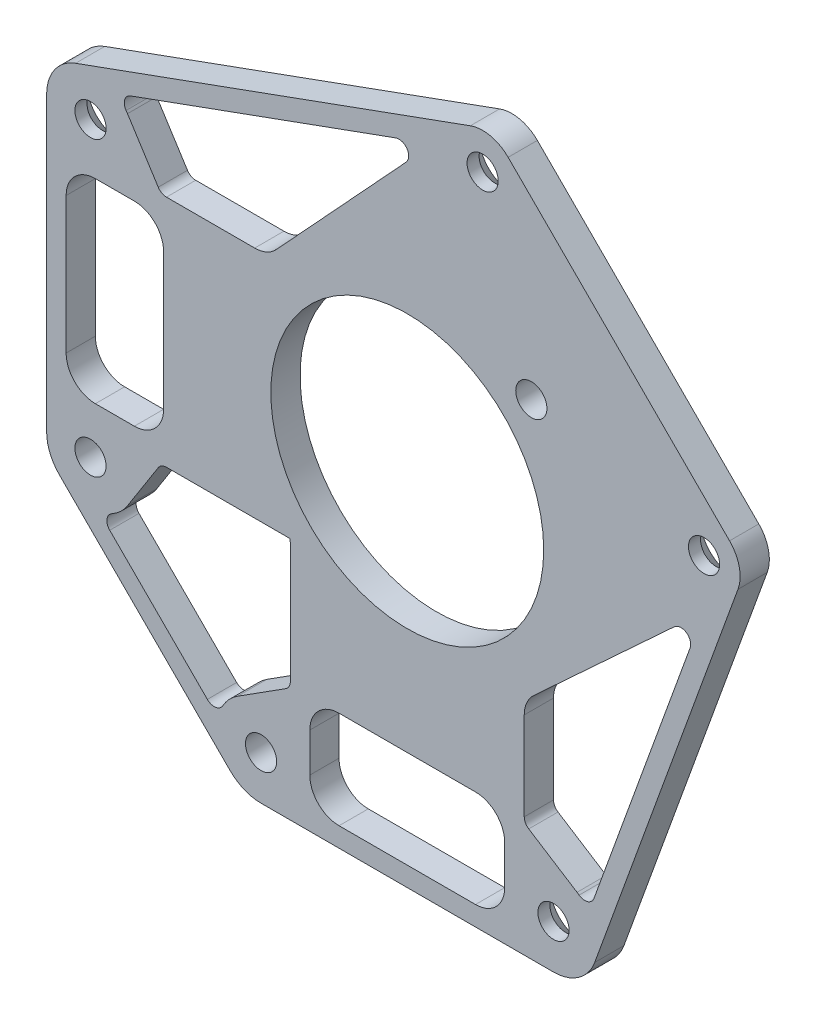
SolidWorks part; units mm, degrees
material "6061-T6 (SS)"
ref_plane "Front Plane" through (0, 0, 0) normal (0, 0, 1) x (1, 0, 0)
ref_plane "Top Plane" through (0, 0, 0) normal (0, 1, 0) x (1, 0, 0)
ref_plane "Right Plane" through (0, 0, 0) normal (1, 0, 0) x (0, 0, -1)
sketch "Sketch1" plane through (0, 0, 0) normal (0, 0, 1) x (1, 0, 0)
  line L0 (-7.7139, 20.2317) -> (-27.0698, -0.7279)
  line L1 (-2.3793, 20.3378) -> (20.3378, -2.3793)
  line L2 (0, 0) -> (-12.7279, -12.7279) construction
  line L8 (-49.7279, -19.7279) -> (-49.7279, -5.7279)
  line L9 (-44.7279, -22.7279) -> (-40.7279, -22.7279)
  line L10 (-47.7279, -19.7279) -> (-47.7279, -5.7279)
  line L11 (-44.7279, -2.7279) -> (-40.7279, -2.7279)
  line L12 (-37.7279, -19.7279) -> (-37.7279, -5.7279)
  line L13 (-47.7279, -22.7279) -> (-37.7279, -2.7279) construction
  line L14 (-47.7279, -2.7279) -> (-37.7279, -22.7279) construction
  line L19 (-44.7279, -0.7279) -> (-40.7279, -0.7279)
  line L21 (-44.7279, -24.7279) -> (-40.7279, -24.7279)
  line L22 (-40.7279, -0.7279) -> (-27.0698, -0.7279)
  line L23 (-40.7279, -24.7279) -> (-24.7695, -24.7279)
  line L24 (20.2317, -7.7139) -> (-0.7279, -27.0698)
  line L25 (-35.7279, -19.7279) -> (-35.7279, -5.7279) construction
  line L26 (-24.7279, -40.7279) -> (-24.7279, -24.7695)
  line L27 (-0.7279, -40.7279) -> (-0.7279, -27.0698)
  line L28 (-2.7279, -47.7279) -> (-22.7279, -37.7279) construction
  line L29 (-22.7279, -47.7279) -> (-2.7279, -37.7279) construction
  line L30 (-24.7279, -44.7279) -> (-24.7279, -40.7279)
  line L31 (-0.7279, -44.7279) -> (-0.7279, -40.7279)
  line L32 (-19.7279, -37.7279) -> (-5.7279, -37.7279)
  line L33 (-2.7279, -44.7279) -> (-2.7279, -40.7279)
  line L34 (-19.7279, -47.7279) -> (-5.7279, -47.7279)
  line L35 (-22.7279, -44.7279) -> (-22.7279, -40.7279)
  line L36 (-19.7279, -49.7279) -> (-5.7279, -49.7279)
  arc A0 (-3.7936, 16.5194) -> (-6.1977, 18.9236) centre (-4.9956, 17.7215) ccw construction
  arc A1 (-6.1977, 18.9236) -> (-3.7936, 16.5194) centre (-4.9956, 17.7215) ccw construction
  arc A2 (-3.7936, 16.5194) -> (-6.1977, 18.9236) centre (-4.9956, 17.7215) ccw construction
  arc A3 (-6.1977, 18.9236) -> (-3.7936, 16.5194) centre (-4.9956, 17.7215) ccw construction
  circle A8 centre (-12.7279, -12.7279) radius 12.7 construction
  circle A9 centre (-12.7279, -12.7279) radius 12.7 construction
  circle A10 centre (-12.7279, -12.7279) radius 14
  arc A11 (-2.3793, 20.3378) -> (-7.7139, 20.2317) centre (-4.9956, 17.7215) ccw
  arc A13 (-24.7695, -24.7279) -> (-24.7279, -24.7695) centre (-12.7279, -12.7279) ccw
  arc A14 (-44.7279, -22.7279) -> (-47.7279, -19.7279) centre (-44.7279, -19.7279) cw
  arc A15 (-40.7279, -22.7279) -> (-37.7279, -19.7279) centre (-40.7279, -19.7279) ccw
  arc A16 (-40.7279, -2.7279) -> (-37.7279, -5.7279) centre (-40.7279, -5.7279) cw
  arc A17 (-47.7279, -5.7279) -> (-44.7279, -2.7279) centre (-44.7279, -5.7279) cw
  arc A18 (-49.7279, -5.7279) -> (-44.7279, -0.7279) centre (-44.7279, -5.7279) cw
  arc A21 (-44.7279, -24.7279) -> (-49.7279, -19.7279) centre (-44.7279, -19.7279) cw
  arc A22 (-40.7279, -24.7279) -> (-35.7279, -19.7279) centre (-40.7279, -19.7279) ccw construction
  arc A23 (-40.7279, -0.7279) -> (-35.7279, -5.7279) centre (-40.7279, -5.7279) cw construction
  arc A24 (-24.7279, -44.7279) -> (-19.7279, -49.7279) centre (-19.7279, -44.7279) ccw
  arc A25 (-5.7279, -49.7279) -> (-0.7279, -44.7279) centre (-5.7279, -44.7279) ccw
  arc A26 (-5.7279, -47.7279) -> (-2.7279, -44.7279) centre (-5.7279, -44.7279) ccw
  arc A27 (-2.7279, -40.7279) -> (-5.7279, -37.7279) centre (-5.7279, -40.7279) ccw
  arc A28 (-22.7279, -40.7279) -> (-19.7279, -37.7279) centre (-19.7279, -40.7279) cw
  arc A29 (-22.7279, -44.7279) -> (-19.7279, -47.7279) centre (-19.7279, -44.7279) ccw
  arc A30 (16.5194, -3.7936) -> (18.9236, -6.1977) centre (17.7215, -4.9956) cw construction
  arc A31 (18.9236, -6.1977) -> (16.5194, -3.7936) centre (17.7215, -4.9956) cw construction
  arc A32 (20.3378, -2.3793) -> (20.2317, -7.7139) centre (17.7215, -4.9956) cw
  point P0 (-42.7279, -12.7279)
  point P5 (0, 0)
  point P20 (0, 0)
  point P42 (0, 0)
  point P63 (-12.7279, -42.7279)
  point P83 (8.9792, 8.9792)
  dimension "D2" = 28
  dimension "D3" = 2
  dimension "D4" = 3
  dimension "D5" = 18.7
  dimension "D9" = 3
  dimension "D6" = 30
  dimension "D7" = 10
  dimension "D8" = 20
  dimension "D10" = 2
extrude "Boss-Extrude1" add sketch "Sketch1" along normal blind 3
fillet "Fillet1" radius 3 3 edges at (-0.7279, -27.0698, 1.5) (-24.7279, -24.7695, 1.5) (-27.0698, -0.7279, 1.5)
hole_wizard "M3 Clearance Hole1" positions "Sketch2" profile "Sketch3" hole size "M3" standard "ANSI Metric" end condition up to next
sketch "Sketch2" plane through (0, 0, 0) normal (0, 0, -1) x (-1, 0, 0)
  point P7 (0, 0)
sketch "Sketch3" plane through (0, 0, 0) normal (1, 0, 0) x (0, 1, 0)
  line L0 (0, 0) -> (0, 3)
  line L1 (0, 3) -> (1.6, 3)
  line L2 (1.6, 3) -> (1.6, 0)
  line L5 (1.6, 0) -> (0, 0)
  line L11 (0, -6.35) -> (0, 107.95) construction
  dimension "Thru Hole Dia." = 3.2
  dimension "Thru Hole Depth" = 3
hole_wizard "CSK for M3 SFHCS1" positions "Sketch4" profile "Sketch5" countersink size "M3" standard "ANSI Metric" end condition up to next
sketch "Sketch4" plane through (0, 0, 0) normal (0, 0, -1) x (-1, 0, 0)
  point P3 (4.9956, 17.7215)
  point P8 (-17.7215, -4.9956)
sketch "Sketch5" plane through (-4.9956, 17.7215, 0) normal (1, 0, 0) x (0, 1, 0)
  line L0 (0, 0) -> (0, 3)
  line L1 (0, 3) -> (1.6, 3)
  line L2 (1.6, 3) -> (1.6, 1.76)
  line L3 (1.6, 1.76) -> (3.36, 0)
  line L5 (3.36, 0) -> (0, 0)
  line L6 (-1.6, 1.76) -> (-3.36, 0) construction
  line L11 (0, -6.35) -> (0, 107.95) construction
  dimension "Thru Hole Dia." = 3.2
  dimension "Thru Hole Depth" = 3
  dimension "Near C'Sink Dia." = 6.72
  dimension "Near C'Sink Angle" = 90
sketch "Sketch8" plane through (0, 0, 3) normal (0, 0, 1) x (1, 0, 0)
  line L0 (-45.2279, -12.7279) -> (-45.2279, 2.2721) construction
  line L1 (-49.7279, -19.7279) -> (-49.7279, -5.7279) construction
  line L2 (-44.7279, -2.7279) -> (-40.7279, -2.7279) construction
  line L3 (-49.7279, 2.2721) -> (-49.7279, -5.7279)
  line L7 (-45.2279, -12.7279) -> (-42.7279, -12.7279) construction
  line L10 (-41.4318, 4.6886) -> (-37.9837, -0.7279)
  line L12 (-42.7279, -12.7279) -> (-42.7279, -2.7279) construction
  line L13 (-40.7279, -0.7279) -> (-27.0698, -0.7279) construction
  line L14 (-44.7279, -0.7279) -> (-37.9837, -0.7279)
  line L15 (-41.4318, -30.1445) -> (-37.9837, -24.7279)
  line L16 (-44.7279, -24.7279) -> (-37.9837, -24.7279)
  line L17 (-49.7279, -27.7279) -> (-49.7279, -19.7279)
  arc A0 (-41.4318, 4.6886) -> (-49.7279, 2.2721) centre (-45.2279, 2.2721) ccw
  arc A3 (-44.7279, -0.7279) -> (-49.7279, -5.7279) centre (-44.7279, -5.7279) ccw construction
  arc A4 (-44.7279, -0.7279) -> (-49.7279, -5.7279) centre (-44.7279, -5.7279) ccw
  arc A7 (-40.7279, -0.7279) -> (-35.7279, -5.7279) centre (-40.7279, -5.7279) cw construction
  arc A8 (-44.7279, -24.7279) -> (-49.7279, -19.7279) centre (-44.7279, -19.7279) cw
  arc A9 (-41.4318, -30.1445) -> (-49.7279, -27.7279) centre (-45.2279, -27.7279) cw
  dimension "D2" = 9
  dimension "D1" = 5
extrude "Boss-Extrude3" add sketch "Sketch8" against normal up to surface (3 mm away) up to face at (-8.3556, 17.7215, 0)
hole_wizard "CSK for M3 SFHCS2" positions "Sketch9" profile "Sketch10" countersink size "M3" standard "ANSI Metric" end condition up to next
sketch "Sketch9" plane through (0, 0, 0) normal (0, 0, -1) x (-1, 0, 0)
  point P0 (45.2279, 2.2721)
sketch "Sketch10" plane through (-45.2279, 2.2721, 0) normal (1, 0, 0) x (0, 1, 0)
  line L0 (0, 0) -> (0, 3)
  line L1 (0, 3) -> (1.6, 3)
  line L2 (1.6, 3) -> (1.6, 1.76)
  line L3 (1.6, 1.76) -> (3.36, 0)
  line L5 (3.36, 0) -> (0, 0)
  line L6 (-1.6, 1.76) -> (-3.36, 0) construction
  line L11 (0, -6.35) -> (0, 107.95) construction
  dimension "Thru Hole Dia." = 3.2
  dimension "Thru Hole Depth" = 3
  dimension "Near C'Sink Dia." = 6.72
  dimension "Near C'Sink Angle" = 90
hole_wizard "M3 Clearance Hole2" positions "Sketch11" profile "Sketch12" hole size "M3" standard "ANSI Metric" end condition up to next
sketch "Sketch11" plane through (0, 0, 0) normal (0, 0, -1) x (-1, 0, 0)
  point P0 (45.2279, -27.7279)
sketch "Sketch12" plane through (-45.2279, -27.7279, 0) normal (1, 0, 0) x (0, 1, 0)
  line L0 (0, 0) -> (0, 3)
  line L1 (0, 3) -> (1.6, 3)
  line L2 (1.6, 3) -> (1.6, 0)
  line L5 (1.6, 0) -> (0, 0)
  line L11 (0, -6.35) -> (0, 107.95) construction
  dimension "Thru Hole Dia." = 3.2
  dimension "Thru Hole Depth" = 3
ref_plane "Plane1" through (0, 0, 0) normal (-0.7071, 0.7071, 0) x (0.7071, 0.7071, 0)
mirror "Mirror1" about plane through (0, 0, 0) normal (-0.7071, 0.7071, 0) of "M3 Clearance Hole2", "CSK for M3 SFHCS2", "Boss-Extrude3"
sketch "Sketch13" plane through (0, 0, 0) normal (0, 0, -1) x (-1, 0, 0)
  line L0 (-21.1996, -6.2577) -> (-6.5022, -46.7628)
  line L1 (-0.2367, -26.179) -> (-20.2317, -7.7139) construction
  line L2 (-17.6929, -10.0584) -> (-20.2317, -7.7139)
  line L3 (-17.6929, -10.0584) -> (-5.8984, -42.5634)
  line L4 (38.8909, -38.8909) -> (-38.8909, 38.8909) construction
  line L5 (10.0584, 17.6929) -> (7.7139, 20.2317)
  line L6 (6.2577, 21.1996) -> (46.7628, 6.5022)
  line L7 (10.0584, 17.6929) -> (42.5634, 5.8984)
  line L8 (30.9099, -48.4099) -> (48.4099, -30.9099)
  line L9 (32.1414, -44.3499) -> (44.3499, -32.1414)
  arc A0 (-20.3378, -2.3793) -> (-20.2317, -7.7139) centre (-17.7215, -4.9956) ccw construction
  arc A1 (-4.6886, -41.4318) -> (-2.2721, -49.7279) centre (-2.2721, -45.2279) ccw construction
  arc A2 (-21.1996, -6.2577) -> (-20.2317, -7.7139) centre (-17.7215, -4.9956) ccw
  arc A3 (-5.8984, -42.5634) -> (-6.5022, -46.7628) centre (-2.2721, -45.2279) ccw
  arc A4 (6.2577, 21.1996) -> (7.7139, 20.2317) centre (4.9956, 17.7215) cw
  arc A5 (42.5634, 5.8984) -> (46.7628, 6.5022) centre (45.2279, 2.2721) cw
  arc A6 (27.7279, -49.7279) -> (30.1445, -41.4318) centre (27.7279, -45.2279) ccw construction
  arc A7 (41.4318, -30.1445) -> (49.7279, -27.7279) centre (45.2279, -27.7279) ccw construction
  arc A8 (44.3499, -32.1414) -> (48.4099, -30.9099) centre (45.2279, -27.7279) ccw
  arc A9 (30.9099, -48.4099) -> (32.1414, -44.3499) centre (27.7279, -45.2279) ccw
  dimension "D1" = 2
  dimension "D2" = 2
extrude "Boss-Extrude4" add sketch "Sketch13" against normal up to surface (3 mm away) up to face at (-29.3279, -45.2279, 3)
fillet "Fillet2" radius 1 10 edges at (-32.1414, -44.3499, 1.5) (-24.7279, -37.9837, 1.5) (-37.9837, -24.7279, 1.5) (-44.3499, -32.1414, 1.5) (5.8984, -42.5634, 1.5) (-0.7279, -37.9837, 1.5) (-42.5634, 5.8984, 1.5) (-37.9837, -0.7279, 1.5) (-10.0584, 17.6929, 1.5) (17.6929, -10.0584, 1.5)
